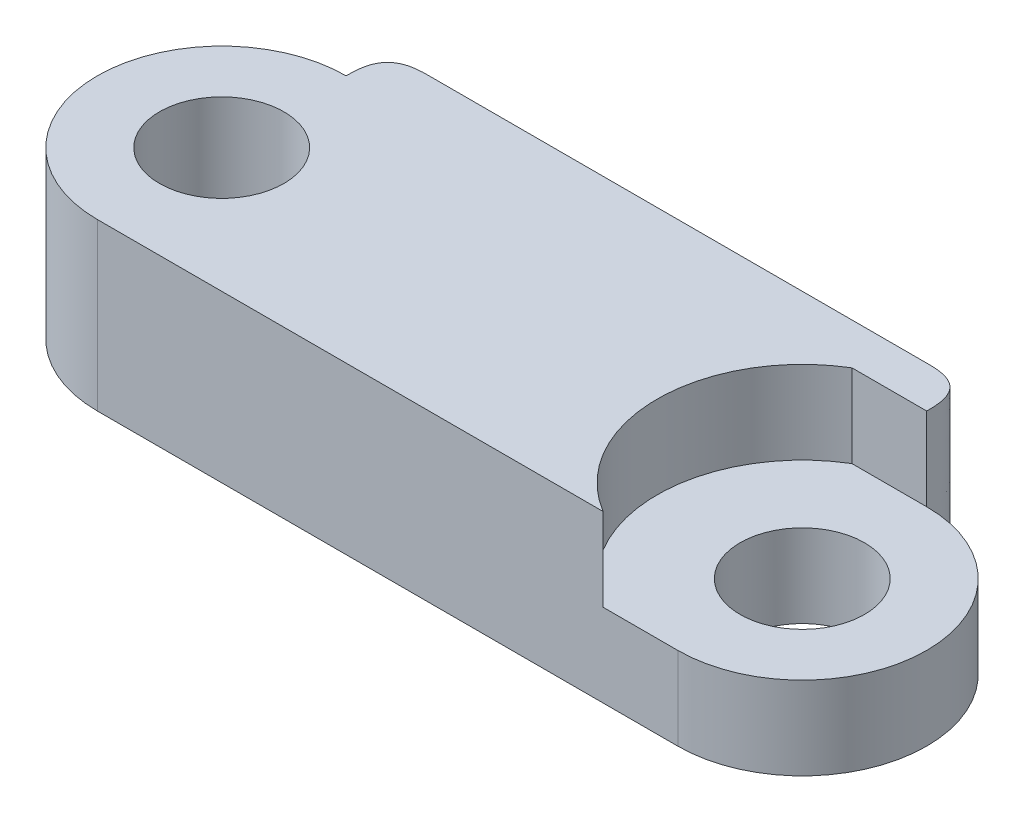
SolidWorks part; units mm, degrees
ref_plane "Front Plane" through (0, 0, 0) normal (0, 0, 1) x (1, 0, 0)
ref_plane "Top Plane" through (0, 0, 0) normal (0, 1, 0) x (1, 0, 0)
ref_plane "Right Plane" through (0, 0, 0) normal (1, 0, 0) x (0, 0, -1)
sketch "Sketch1" plane through (0, 0, 0) normal (0, 1, 0) x (1, 0, 0)
  line L0 (-7, 0) -> (7, 0) construction
  line L1 (-7, 3) -> (7, 3)
  line L2 (-7, -3) -> (7, -3)
  arc A0 (-7, 3) -> (-7, -3) centre (-7, 0) ccw
  arc A1 (7, -3) -> (7, 3) centre (7, 0) ccw
  circle A2 centre (-7, 0) radius 1.5
  circle A3 centre (7, 0) radius 1.5
  point P3 (0, 0)
  point P9 (-10, 0)
  point P10 (10, 0)
  dimension "D3" = 3
  dimension "D4" = 3
  dimension "D1" = 6
  dimension "D2" = 20
extrude "Boss-Extrude1" add sketch "Sketch1" along normal mid plane 4
sketch "Sketch2" plane through (0, 2, 0) normal (0, 1, 0) x (1, 0, 0)
  line L0 (5.1972, 3) -> (7, 3)
  line L1 (7, 3) -> (-7, 3) construction
  line L2 (-7, -3) -> (7, -3) construction
  line L3 (7, -3) -> (5.1972, -3)
  arc A0 (7, 3) -> (7, -3) centre (7, 0) cw
  arc A1 (5.1972, -3) -> (5.1972, 3) centre (7, 0) cw
  dimension "D1" = 3.5
extrude "Cut-Extrude1" cut sketch "Sketch2" against normal blind 2
sketch "Sketch3" plane through (0, -2, 0) normal (0, -1, 0) x (1, 0, 0)
  line L0 (7, -3) -> (7, -4)
  line L1 (7, -4) -> (-7, -4)
  line L2 (-7, -4) -> (-7, -3)
  line L3 (-7, -3) -> (7, -3)
  dimension "D1" = 1
extrude "Boss-Extrude2" add sketch "Sketch3" against normal up to surface (4 mm away) up to face at (-2.0757, 2, 0)
fillet "Fillet1" radius 1 2 edges at (7, 0, -4) (-7, 0, -4) curvature continuous yes
